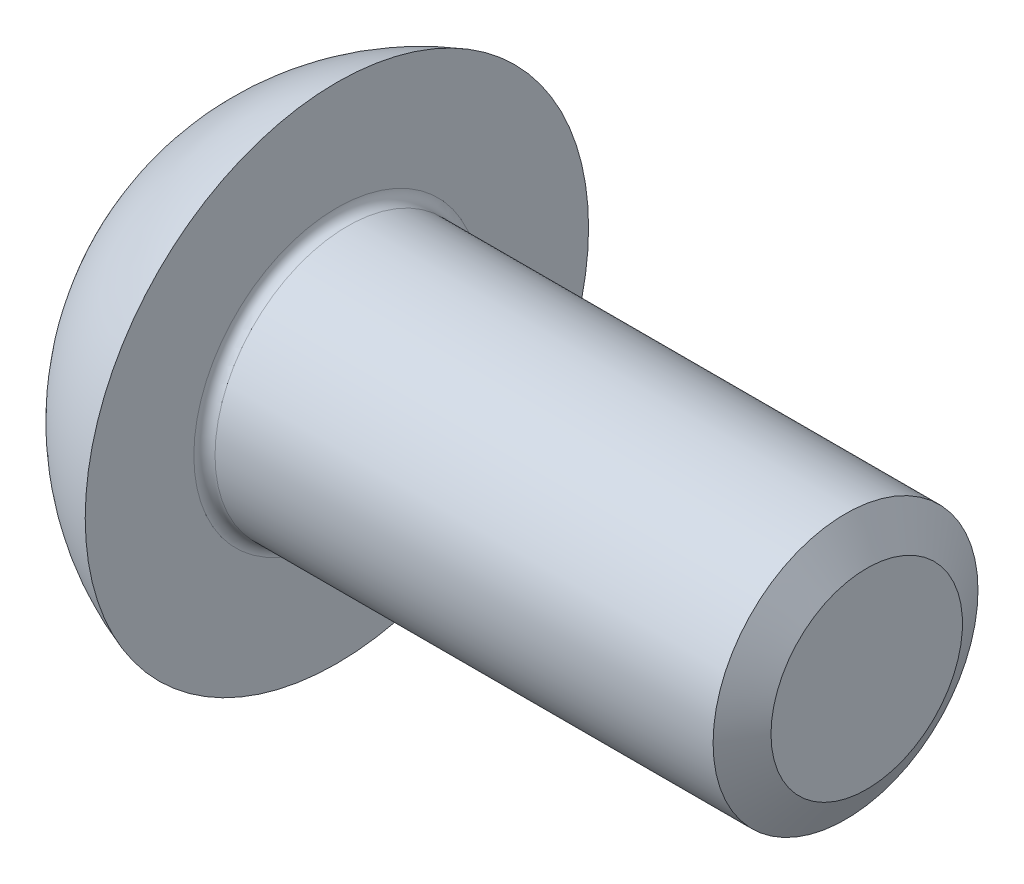
SolidWorks part; units mm, degrees
material "8.8级"
ref_plane "前视基准面" through (0, 0, 0) normal (0, 0, 1) x (1, 0, 0)
ref_plane "上视基准面" through (0, 0, 0) normal (0, 1, 0) x (1, 0, 0)
ref_plane "右视基准面" through (0, 0, 0) normal (1, 0, 0) x (0, 0, -1)
sketch "草图1" plane through (0, 0, 0) normal (0, 0, 1) x (1, 0, 0)
  line L0 (-12.75, 0) -> (0, 0) construction
  line L1 (0, 2.5) -> (-9.8, 2.5)
  line L2 (-10, 2.7) -> (-10, 4.75)
  line L3 (-12.75, 0) -> (-12.75, 2.5)
  line L4 (0, 2.5) -> (0, 0)
  line L5 (-12.75, 0) -> (0, 0)
  arc A0 (-10, 4.75) -> (-12.75, 2.5) centre (-8.4091, 0) ccw
  arc A1 (-9.8, 2.5) -> (-10, 2.7) centre (-9.8, 2.7) cw
  point P10 (-10, 2.5)
  dimension "r" = 0.2
  dimension "d" = 5
  dimension "dk" = 9.5
  dimension "k" = 2.75
  dimension "l" = 10
revolve "旋转1" add sketch "草图1" angle 360 about L0
cosmetic thread "装饰螺纹线1" parameters "D1"=2, "D2"=4.3
sketch "草图2" plane through (-12.75, 0, 0) normal (-1, 0, 0) x (0, 0, 1)
  line L1 (0, 1.7321) -> (-1.5, 0.866)
  line L2 (-1.5, 0.866) -> (-1.5, -0.866)
  line L3 (-1.5, -0.866) -> (0, -1.7321)
  line L4 (0, -1.7321) -> (1.5, -0.866)
  line L5 (1.5, -0.866) -> (1.5, 0.866)
  line L6 (1.5, 0.866) -> (0, 1.7321)
  circle A0 centre (0, 0) radius 1.5 construction
  dimension "s" = 3
extrude "切除-拉伸1" cut sketch "草图2" against normal blind 2.75
sketch "草图6" plane through (0, 0, 0) normal (0, 0, 1) x (1, 0, 0)
  line L0 (-11.19, 1.7321) -> (-10, 0)
  line L1 (-9.56, 1.7321) -> (-9.56, 0)
  line L2 (-9.56, 1.7321) -> (-11.19, 1.7321)
  line L3 (-12.75, 0) -> (-10, 0) construction
  line L4 (-9.56, 0) -> (-10, 0)
  line L5 (-12.75, 0) -> (-16.19, 0) construction
  dimension "t" = 1.56
  dimension "e-s" = 0.44
  dimension "k" = 2.75
  dimension "e" = 3.44
revolve "旋转2" add sketch "草图6" angle 360 about L3
sketch "草图7" plane through (0, 0, 0) normal (0, 0, 1) x (1, 0, 0)
  line L3 (-12.75, 1.7321) -> (-12.31, 0)
  line L4 (-12.75, 0) -> (-12.31, 0) construction
  line L7 (-12.75, 1.7321) -> (-12.75, 0)
  line L8 (-12.75, 0) -> (-12.31, 0)
  dimension "e-s" = 0.44
revolve "切除-旋转5" cut sketch "草图7" angle 360 about L4
sketch "草图4" plane through (0, 0, 0) normal (0, 0, 1) x (1, 0, 0)
  line L0 (-0.4, 2.5) -> (0, 1.8072)
  line L1 (-0.4, 2.5) -> (0.4, 2.5)
  line L2 (0.4, 2.5) -> (0, 1.8072)
  line L4 (0, -2.5) -> (0, 2.5) construction
  line L5 (-0.4, 0) -> (0.4, 0) construction
  dimension "d" = 2.5
  dimension "p" = 0.8
revolve "切除-旋转1" cut sketch "草图4" angle 360 about L5
ref_axis "基准轴1" through (-8.1887, 0, 0) along (1, 0, 0)
pattern_linear "阵列(线性)1" [suppressed] count 3 spacing 0.8 along (-1, 0, 0) of bodies 104
equation "\"D2@装饰螺纹线1\" = \"d@草图1\" * 0.86"
equation "\"k@草图6\" = \"k@切除-拉伸1\""
equation "\"e-s@草图6\" = \"e@草图6\" - \"s@草图2\""
equation "\"e-s@草图7\" = \"e-s@草图6\""
equation "\"d@草图4\" = \"d@草图1\" / 2"
equation "\"k@切除-拉伸1\" = \"k@草图1\""
equation "\"D1@阵列(线性)1\" = \"D1@装饰螺纹线1\" / \"p@草图4\""
equation "\"D3@阵列(线性)1\" = \"p@草图4\""
